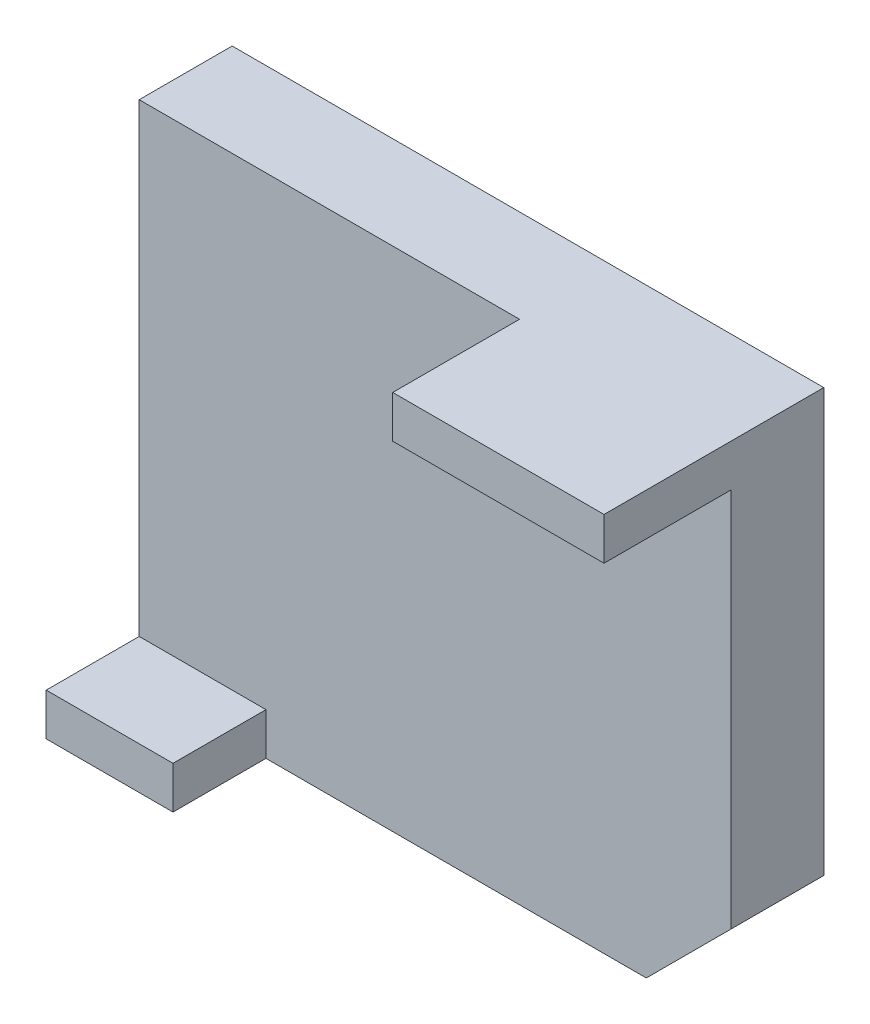
SolidWorks part; units mm, degrees
ref_plane "Front Plane" through (0, 0, 0) normal (0, 0, 1) x (1, 0, 0)
ref_plane "Top Plane" through (0, 0, 0) normal (0, 1, 0) x (1, 0, 0)
ref_plane "Right Plane" through (0, 0, 0) normal (1, 0, 0) x (0, 0, -1)
sketch "Sketch1" plane through (0, 0, 0) normal (0, 0, 1) x (1, 0, 0)
  line L0 (0, 0) -> (0, -120)
  line L1 (0, 0) -> (140, 0)
  line L2 (0, -120) -> (30, -120)
  line L3 (30, -120) -> (30, -110)
  line L4 (30, -110) -> (0, -110)
  line L5 (140, 0) -> (140, -100)
  line L6 (140, -100) -> (120, -120)
  line L7 (120, -120) -> (30, -120)
  line L8 (90, -10) -> (110, -10)
  line L9 (90, -10) -> (90, 0)
  line L10 (110, 0) -> (110, -10)
  line L11 (110, -10) -> (140, -10)
  dimension "D1" = 10
  dimension "D2" = 30
  dimension "D3" = 10
  dimension "D4" = 120
  dimension "D5" = 140
  dimension "D6" = 20
  dimension "D7" = 20
  dimension "D8" = 30
  dimension "D9" = 20
extrude "Boss-Extrude1" add sketch "Sketch1" along normal blind 22 contours L9 L1 L0 L4 L3 L7 L6 L5 region at (68.8186, -60.0211, 0)
extrude "Boss-Extrude2" add sketch "Sketch1<3>" along normal blind 44 contours L3 L4 L0 L2 region at (15, -115, 0)
sketch "Sketch1<3>" plane through (0, 0, 0) normal (0, 0, 1) x (1, 0, 0) same geometry as "Sketch1"
extrude "Boss-Extrude3" add sketch "Sketch1<4>" along normal blind 52 contours L9 L5 L1 region at (125, -5, 0)
sketch "Sketch1<4>" plane through (0, 0, 0) normal (0, 0, 1) x (1, 0, 0) same geometry as "Sketch1"
extrude "Boss-Extrude4" add sketch "Sketch1<5>" along normal blind 52 contours L10 L1 L9 L8 region at (100, -5, 0)
sketch "Sketch1<5>" plane through (0, 0, 0) normal (0, 0, 1) x (1, 0, 0) same geometry as "Sketch1"
